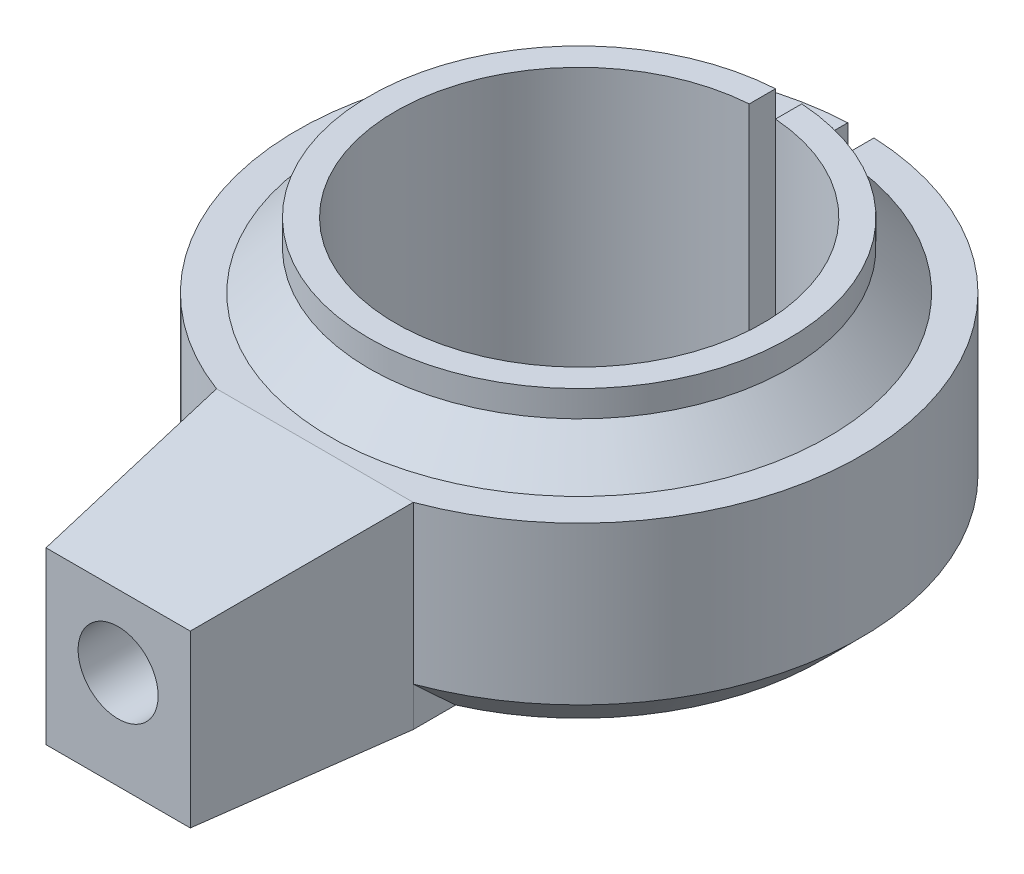
SolidWorks part; units mm, degrees
ref_plane "Front Plane" through (0, 0, 0) normal (0, 0, 1) x (1, 0, 0)
ref_plane "Top Plane" through (0, 0, 0) normal (0, 1, 0) x (1, 0, 0)
ref_plane "Right Plane" through (0, 0, 0) normal (1, 0, 0) x (0, 0, -1)
sketch "Sketch1" plane through (0, 0, 0) normal (0, 1, 0) x (1, 0, 0)
  line L0 (-16.7192, 17.9567) -> (-16.7192, 25.4692)
  line L2 (-23.2192, -16.1569) -> (-8.2192, -16.1569)
  line L3 (-23.2192, -16.1569) -> (-23.2192, -31.1569)
  line L4 (-23.2192, -31.1569) -> (-8.2192, -31.1569)
  line L5 (-8.2192, -16.1569) -> (-8.2192, -31.1569)
  line L9 (-16.7192, 25.4692) -> (-14.7192, 25.4692)
  line L10 (-14.7192, 25.4692) -> (-14.7192, 17.9567)
  circle A0 centre (-15.7192, 3.9925) radius 14
  circle A1 centre (-15.7192, 3.9925) radius 21.5
  dimension "D1" = 28
  dimension "D4" = 43
  dimension "D2" = 15
  dimension "D3" = 15
  dimension "D8" = 2
  dimension "D9" = 1
extrude "Boss-Extrude1" add sketch "Sketch1" along normal blind 15 contours A0 L0 L3 L10 | L3 L4 L5 L2 region at (-25.6664, 0, 6.6925)
sketch "Sketch2" plane through (0, 0, 31.1569) normal (0, 0, 1) x (1, 0, 0)
  circle A0 centre (-15.7192, 7.5) radius 3.05
  dimension "D1" = 6.1
extrude "Cut-Extrude1" cut sketch "Sketch2" against normal blind 15
sketch "Sketch3" plane through (0, 15, 0) normal (0, 1, 0) x (1, 0, 0)
  line L0 (-16.7192, 19.9612) -> (-16.7192, 17.9567)
  line L1 (-14.7192, 17.9567) -> (-14.7192, 19.9612)
  line L2 (-14.7192, 25.4692) -> (-14.7192, 17.9567) construction
  line L3 (-16.7192, 17.9567) -> (-16.7192, 25.4692) construction
  circle A0 centre (-15.7192, 3.9925) radius 16
  circle A1 centre (-15.7192, 3.9925) radius 12.25
  line M4 (-14.7192, 25.4692) -> (-14.7192, 17.9567)
  arc M5 (-14.7192, 17.9567) -> (-16.7192, 17.9567) centre (-15.7192, 3.9925) cw
  line M6 (-16.7192, 17.9567) -> (-16.7192, 25.4692)
  dimension "D1" = 32
extrude "Boss-Extrude2" add sketch "Sketch3" along normal blind 5 contours A0 M6 M4 M5 region at (-17.1715, 15, -18.959)
chamfer "Chamfer4" distance 3 angle 45 3 edges at (-15.7192, 15, 12.0075) (5.5234, 0, -7.3096) (-36.9618, 0, -7.3096)
chamfer "Chamfer6" distance 15 distance2 2 3 edges at (-8.2192, 7.5, 31.1569) (-15.7192, 15, 31.1569) (-23.2192, 7.5, 31.1569) first distance on face at (-8.2192, 6.3, 21.1856) first distance on face at (-15.7192, 15, 3.803) first distance on face at (-23.2192, 6.9, 21.8332)
sketch "Sketch4" plane through (-14.7192, 0, 0) normal (-1, 0, 0) x (0, 0, 1)
  line L0 (-22.4654, 0) -> (-17.9567, 0) construction
  line L2 (-25.4692, 15) -> (-25.4692, 3) construction
  circle A0 centre (-21.4692, 7.5) radius 1.5
  dimension "D1" = 3
  dimension "D2" = 7.5
  dimension "D3" = 4
extrude "Cut-Extrude2" cut sketch "Sketch4" against normal blind 25 and the other way blind 29
ref_plane "Plane1" through (5.7808, 0, 0) normal (1, 0, 0) x (0, 0, -1)
sketch "Sketch5" plane through (5.7808, 0, 0) normal (1, 0, 0) x (0, 0, -1)
  circle A0 centre (21.4692, 7.5) radius 2.5
  dimension "D1" = 5
extrude "Cut-Extrude3" cut sketch "Sketch5" against normal up to surface (20.5 mm away) up to face at (-14.7192, 7.5, -22.9692)
ref_plane "Plane2" through (-37.2192, 0, 0) normal (-1, 0, 0) x (0, 0, 1)
sketch "Sketch6" plane through (-37.2192, 0, 0) normal (-1, 0, 0) x (0, 0, 1)
  circle A0 centre (-21.4692, 7.5) radius 3
  dimension "D1" = 6
extrude "Cut-Extrude4" cut sketch "Sketch6" against normal offset from surface (15.5 mm away) 5 up to face at (-16.7192, 7.5, -19.9692)
